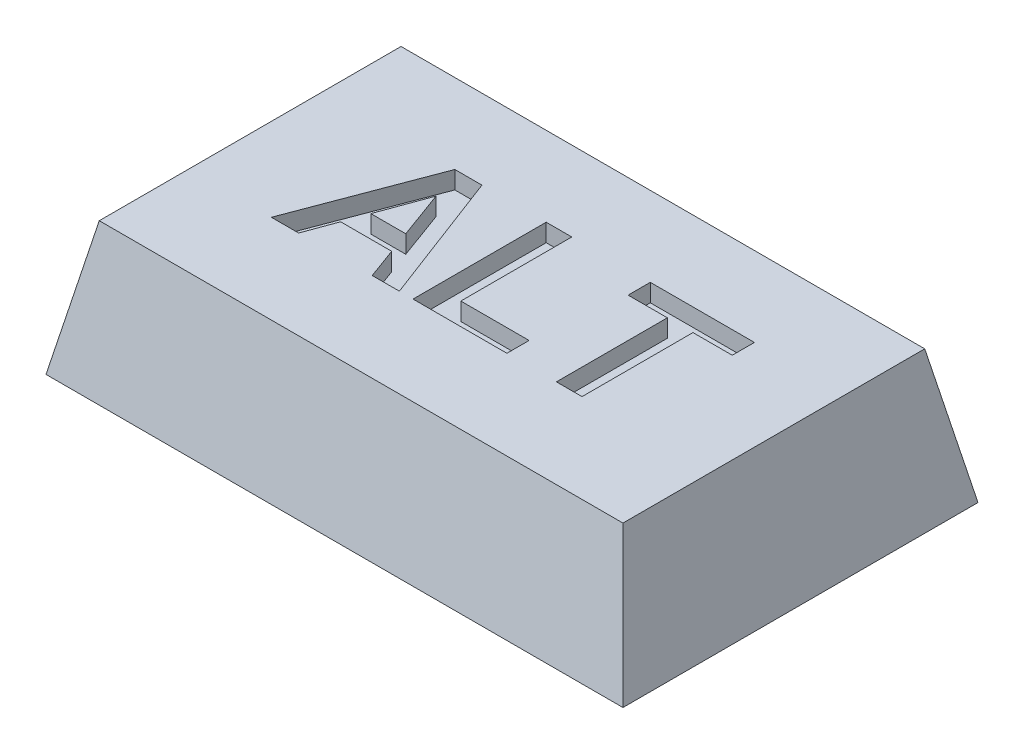
SolidWorks part; units mm, degrees
ref_plane "Front Plane" through (0, 0, 0) normal (0, 0, 1) x (1, 0, 0)
ref_plane "Top Plane" through (0, 0, 0) normal (0, 1, 0) x (1, 0, 0)
ref_plane "Right Plane" through (0, 0, 0) normal (1, 0, 0) x (0, 0, -1)
sketch "Sketch1" plane through (0, 0, 0) normal (0, 1, 0) x (1, 0, 0)
  line L1 (0, 0) -> (13, 0)
  line L2 (0, 0) -> (0, 8)
  line L3 (0, 8) -> (13, 8)
  line L4 (13, 0) -> (13, 8)
  dimension "D1" = 8
  dimension "D2" = 13
extrude "Boss-Extrude1" add sketch "Sketch1" along normal blind 3
sketch "Sketch2" plane through (0, 0, 0) normal (0, 0, 1) x (1, 0, 0)
  line L0 (0, 0) -> (0.6, 3)
  line L1 (0, 3) -> (13, 3) construction
  line L2 (0.6, 3) -> (0, 3)
  line L3 (0, 3) -> (0, 0)
  line L4 (13, 0) -> (12.4, 3)
  line L5 (12.4, 3) -> (13, 3)
  line L6 (13, 3) -> (13, 0)
  dimension "D1" = 0.6
  dimension "D2" = 0.6
extrude "Cut-Extrude1" cut sketch "Sketch2" against normal through all both and the other way through all
sketch "Sketch3" plane through (0, 0, 0) normal (1, 0, 0) x (0, 0, -1)
  line L0 (0, 0) -> (0.6, 3)
  line L1 (8, 3) -> (0, 3) construction
  line L2 (0.6, 3) -> (0, 3)
  line L3 (0, 3) -> (0, 0)
  line L4 (8, 3) -> (7.4, 3)
  line L5 (7.4, 3) -> (8, 0)
  line L6 (8, 3) -> (8, 0)
  dimension "D1" = 0.6
  dimension "D2" = 0.6
extrude "Cut-Extrude2" cut sketch "Sketch3" along normal through all both and the other way through all
sketch "Sketch4" plane through (0, 0, 0) normal (0, -1, 0) x (1, 0, 0)
  line L1 (6.5, 0) -> (6.5, -8) construction
  line L2 (13, -8) -> (0, -8) construction
  line L3 (0, 0) -> (13, 0) construction
  circle A0 centre (6.5, -3.75) radius 1.75
  dimension "D1" = 3.5
  dimension "D2" = 0
  dimension "D3" = 3.75
extrude "Cut-Extrude3" cut sketch "Sketch4" against normal blind 0.4
sketch "Sketch5" plane through (0, 0, 0) normal (0, -1, 0) x (1, 0, 0)
  line L5 (0, 0) -> (13, 0) construction
  line L6 (2.5, -8) -> (10.5, -8)
  line L7 (2.5, -8) -> (2.5, -6.9)
  line L8 (2.5, -6.9) -> (10.5, -6.9)
  line L9 (10.5, -8) -> (10.5, -6.9)
  point P2 (6.5, 0)
  dimension "D1" = 1.1
  dimension "D2" = 4
  dimension "D3" = 4
extrude "Boss-Extrude2" add sketch "Sketch5" along normal blind 2
fillet "Fillet1" radius 4 2 edges at (10.5, -2, -7.45) (2.5, -2, -7.45)
sketch "Sketch6" plane through (0, 3, 0) normal (0, 1, 0) x (1, 0, 0)
  text T0 "ALT" font "Arial" height 3
extrude "Cut-Extrude4" cut sketch "Sketch6" against normal blind 0.4
